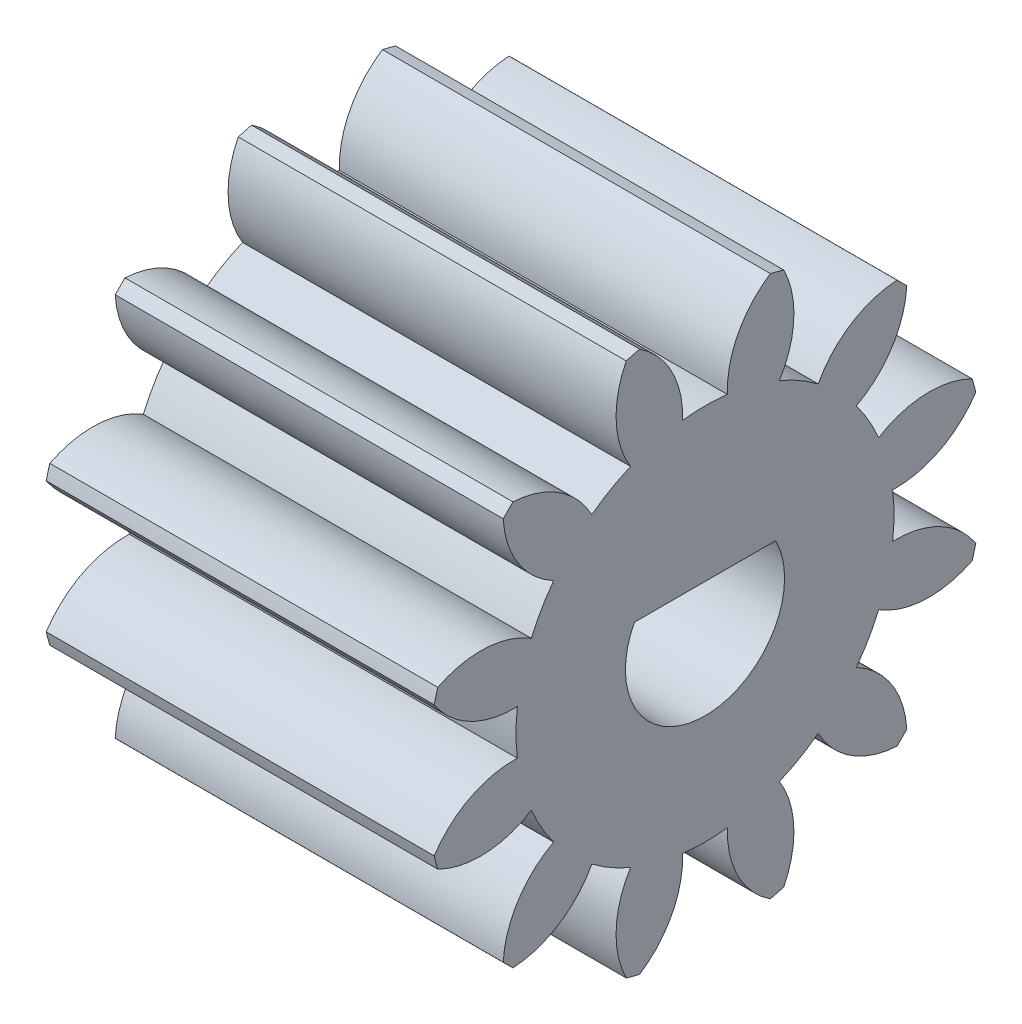
SolidWorks part; units mm, degrees
ref_plane "Plane1" through (0, 0, 0) normal (0, 0, 1) x (1, 0, 0)
ref_plane "Plane2" through (0, 0, 0) normal (0, 1, 0) x (1, 0, 0)
ref_plane "Plane3" through (0, 0, 0) normal (1, 0, 0) x (0, 0, -1)
sketch "HoldingSke" plane through (0, 0, 0) normal (0, 1, 0) x (1, 0, 0)
  line L0 (0, 0) -> (631.0617, -134.1363)
  line L1 (-15, 0) -> (100, 0) construction
  line L2 (0, 0) -> (-2.1039, 2.3779)
  line L3 (0, 0) -> (-11.863, 4.5341)
  line L4 (0, 0) -> (8.4473, 1.7955)
  line L5 (0, 0) -> (-46.8476, -17.4728)
  line L6 (0, 0) -> (-9.9476, -6.7116)
  line L7 (-2.1039, 2.3779) -> (8.6589, 51.2071)
  line L8 (-76.2, 54.61) -> (-76.1, 54.61)
  line L9 (-71.009, 38.7566) -> (-53.1078, 45.2721)
  line L10 (-76.2, 71.12) -> (104.1128, 71.12)
  line L11 (0, 0) -> (-12, 0)
  line L12 (-76.2, 101.6) -> (-76.162, 101.6)
  line L13 (24.9733, 27.94) -> (52.9518, 28.4284)
  line L14 (24.9733, 27.94) -> (24.9743, 27.94)
  line L15 (24.9733, 27.94) -> (100.4006, 29.5858)
  line L16 (-63.627, -1) -> (-12.827, -1)
  circle A0 centre (0, 0) radius 0.4
  circle A1 centre (0, 0) radius 4.749
  circle A2 centre (0, 0) radius 37.5
  circle A3 centre (0, 0) radius 0.4
  dimension "MHD" = 9.498
  dimension "Hub_dia" = 75
  dimension "Bore" = 0.8
  dimension "MBD" = 0.8
  dimension "Num_teeth" = 12
  dimension "Pitch" = 645.16
  dimension "Overall_len" = 50
  dimension "Show_teeth" = 12
  dimension "Thickness" = 12
  dimension "OAL" = 50.0013
  dimension "T_dim" = 0.1
  dimension "Ap" = 20
  dimension "H" = 19.05
  dimension "Pitch_radius" = 180.3128
  dimension "Width" = 12
  dimension "Backlash" = 0.038
  dimension "Addendum_fac" = 1
  dimension "Dedendum_fac" = 1.25
  dimension "Clearance_fac" = 0.25
  dimension "Dedendum_add" = 0.001
  dimension "Module" = 1
sketch "BasProSke" plane through (0, 0, 0) normal (0, 1, 0) x (1, 0, 0)
  line L0 (-10, 0) -> (60, 0) construction
  line L1 (0, 0) -> (0, 7)
  line L2 (0, 0) -> (9.75, 0)
  line L3 (9.75, 0) -> (9.75, 7)
  line L4 (9.75, 7) -> (0, 7)
  dimension "Thickness" = 9.75
  dimension "Diameter" = 14
revolve "Base-Revolve" add sketch "BasProSke" angle 360 about L0
sketch "TooCutSke" plane through (0, 0, 0) normal (1, 0, 0) x (0, 0, -1)
  line L1 (0, 0) -> (0, 107) construction
  line L2 (0, 0) -> (-0.8496, 5.9395) construction
  line L3 (0, 0) -> (-3.0836, 11.5081) construction
  line L4 (-0.8496, 5.9395) -> (-1.5418, 5.7541) construction
  arc A0 (0.5622, 4.7156) -> (-0.5622, 4.7156) centre (0, 0) ccw
  arc A1 (2.6365, 7.1762) -> (-2.6365, 7.1762) centre (0, 0) ccw
  circle A2 centre (0, 0) radius 6 construction
  circle A3 centre (0, 0) radius 5.6382 construction
  arc A4 (-0.5622, 4.7156) -> (-2.6365, 7.1762) centre (-2.9608, 4.7982) ccw
  arc A5 (2.6365, 7.1762) -> (0.5622, 4.7156) centre (2.9608, 4.7982) ccw
  dimension "Root_dia" = 9.498
  dimension "Overcut_dia" = 15.2903
  dimension "Pitch_dia" = 12
  dimension "Base_dia" = 11.2763
  dimension "Flank_rad" = 2.4
  dimension "Half_ang" = 15
  dimension "Half_CT" = 0.7167
extrude "ToothCut" cut sketch "TooCutSke" along normal through all
fillet "Breaks" [suppressed] radius 0.02 tangent propagation no
fillet "RootFillets" [suppressed] radius 0.251
pattern_circular "TeethCuts" count 12 every 30 about axis through (-10, 0, 0) along (1, 0, 0) of "ToothCut", "RootFillets", "Breaks"
sketch "HubNeaOneSke" plane through (0, 0, 0) normal (-1, 0, 0) x (0, 0, 1)
  circle A0 centre (0, 0) radius 4.749
  dimension "Diameter" = 9.498
extrude "HubNearOne" [suppressed] add sketch "HubNeaOneSke" along normal blind 40.2513
sketch "HubNeaBotSke" plane through (0, 0, 0) normal (-1, 0, 0) x (0, 0, 1)
  circle A0 centre (0, 0) radius 4.749
  dimension "Diameter" = 9.498
extrude "HubNearBoth" [suppressed] add sketch "HubNeaBotSke" along normal blind 20.1256
ref_plane "FarPln" through (9.75, 0, 0) normal (1, 0, 0) x (0, 0, -1)
sketch "HubFarSke" plane through (9.75, 0, 0) normal (1, 0, 0) x (0, 0, -1)
  circle A0 centre (0, 0) radius 4.749
  dimension "Diameter" = 9.498
extrude "HubFar" [suppressed] add sketch "HubFarSke" along normal blind 20.1256
sketch "BorSke" plane through (0, 0, 0) normal (1, 0, 0) x (0, 0, -1)
  circle A0 centre (0, 0) radius 0.4
  dimension "Diameter" = 0.8
extrude "Bore" cut sketch "BorSke" along normal mid plane 100.0026
sketch "KeySke" plane through (0, 0, 0) normal (1, 0, 0) x (0, 0, -1)
  line L0 (-0.05, 0) -> (-0.05, 0.5)
  line L1 (-0.05, 0.5) -> (0.05, 0.5)
  line L2 (0.05, 0.5) -> (0.05, 0)
  line L3 (0, 0) -> (0, 34) construction
  line L4 (-0.05, 0) -> (0.05, 0)
  dimension "Offset" = 0.5
  dimension "Width" = 0.1
extrude "Keyway" [suppressed] cut sketch "KeySke" along normal mid plane 100.0026
pattern_circular "Keyway2" [suppressed] count 2 every 90 about axis through (-10, 0, 0) along (1, 0, 0) reverse direction yes
sketch "Sketch1" plane through (0, 0, 0) normal (-1, 0, 0) x (0, 0, 1)
  circle A0 centre (0, 0) radius 7
scale "Scale1" scale about centroid uniform scaling yes scale factor 2
sketch "Sketch4" plane through (14.625, 0, 0) normal (1, 0, 0) x (0, 0, -1)
  line L2 (0, 1.85) -> (-3.5465, 1.85)
  line L3 (0, 1.85) -> (3.5465, 1.85)
  arc A0 (-3.5465, 1.85) -> (3.5465, 1.85) centre (0, 0) ccw
extrude "Cut-Extrude1" cut sketch "Sketch4" against normal blind 15
sketch "Sketch5" plane through (-4.875, 0, 0) normal (-1, 0, 0) x (0, 0, 1)
  circle A0 centre (0, 0) radius 4
extrude "Cut-Extrude2" cut sketch "Sketch5" against normal blind 5
sketch "Sketch6" plane through (14.625, 0, 0) normal (1, 0, 0) x (0, 0, -1)
  circle A0 centre (0, 0) radius 11.811 construction
  dimension "D1" = 23.622
equation "' \"Module@HoldingSke\" = 6.35"
equation "' \"Num_teeth@HoldingSke\" = 12"
equation "' \"Ap@HoldingSke\" =  20"
equation "' \"Ap@HoldingSke\" = 20"
equation "' \"Width@HoldingSke\" = 0.5 * 25.4"
equation "' \"Hub_dia@HoldingSke\"= 1 * 25.4"
equation "' \"Hub_dia@HoldingSke\" = 1 * 25.4"
equation "' \"Overall_len@HoldingSke\" = 1.0 * 25.4"
equation "' \"Bore@HoldingSke\" = 0.75 * 25.4"
equation "' \"T_dim@HoldingSke\" = 0.1 * 25.4"
equation "' \"Width@KeySke\" = 0.25 * 25.4"
equation "' \"Show_teeth@HoldingSke\" = 13"
equation "' \"Backlash@HoldingSke\" = 0.009 * 25.4"
equation "' \"Addendum_fac@HoldingSke\" = 1.0"
equation "' \"Dedendum_fac@HoldingSke\" = 1.25"
equation "' \"Dedendum_add@HoldingSke\" = 0.00005 * 25.4"
equation "' \"Clearance_fac@HoldingSke\" = 0.25"
equation "\"Pitch@HoldingSke\" = 1 / \"Module@HoldingSke\""
equation "\"Overcut_dia@TooCutSke\" = (\"Num_teeth@HoldingSke\" + 2 * \"Addendum_fac@HoldingSke\") / \"Pitch@HoldingSke\" + 0.002 * 25.4"
equation "\"Pitch_dia@TooCutSke\" = \"Num_teeth@HoldingSke\" / \"Pitch@HoldingSke\""
equation "\"Base_dia@TooCutSke\" = \"Num_teeth@HoldingSke\" / \"Pitch@HoldingSke\" * cos((\"Ap@HoldingSke\"  * 3.14159265 / 180))"
equation "\"Root_dia@TooCutSke\" = (\"Num_teeth@HoldingSke\" + 2) / \"Pitch@HoldingSke\" - 2 * (\"Addendum_fac@HoldingSke\" + \"Dedendum_fac@HoldingSke\") / \"Pitch@HoldingSke\" - \"Dedendum_add@HoldingSke\" * 2"
equation "\"Half_ang@TooCutSke\" = 180 / \"Num_teeth@HoldingSke\""
equation "\"Half_CT@TooCutSke\" = \"Num_teeth@HoldingSke\" / \"Pitch@HoldingSke\" * sin((3.14159265 / 2 / \"Num_teeth@HoldingSke\")) / 2 - 7 * \"Backlash@HoldingSke\" / 4"
equation "\"Flank_rad@TooCutSke\" = \"Num_teeth@HoldingSke\" / \"Pitch@HoldingSke\" / 5"
equation "\"Radius@RootFillets\" = \"Clearance_fac@HoldingSke\" / \"Pitch@HoldingSke\" + \"Dedendum_add@HoldingSke\""
equation "\"Break_rad@Breaks\" = 0.02 / \"Pitch@HoldingSke\""
equation "\"Thickness@HoldingSke\" = \"Width@HoldingSke\""
equation "\"OAL@HoldingSke\" = \"Thickness@HoldingSke\""
equation "\"MHD@HoldingSke\" = (\"Num_teeth@HoldingSke\" + 2) / \"Pitch@HoldingSke\" - 2 * (\"Addendum_fac@HoldingSke\" + \"Dedendum_fac@HoldingSke\")  / \"Pitch@HoldingSke\" - \"Dedendum_add@HoldingSke\" * 2"
equation "\"MBD@HoldingSke\" = (\"Num_teeth@HoldingSke\" + 2) / \"Pitch@HoldingSke\" - 2 * (\"Addendum_fac@HoldingSke\" + \"Dedendum_fac@HoldingSke\")  / \"Pitch@HoldingSke\" - \"Dedendum_add@HoldingSke\" * 2 - 0.002 * 25.4"
equation "\"MHD@HoldingSke\" = ((sgn( \"MHD@HoldingSke\" - \"Hub_dia@HoldingSke\" )-1)*( \"MHD@HoldingSke\" - \"Hub_dia@HoldingSke\" ))/-2+ \"Hub_dia@HoldingSke\""
equation "\"MBD@HoldingSke\" = ((sgn( \"MBD@HoldingSke\" - \"Bore@HoldingSke\" )-1)*( \"MBD@HoldingSke\" - \"Bore@HoldingSke\" ))/-2+ \"Bore@HoldingSke\""
equation "\"OAL@HoldingSke\" = ((sgn( \"OAL@HoldingSke\" - \"Overall_len@HoldingSke\" )+1)*( \"OAL@HoldingSke\" - \"Overall_len@HoldingSke\" ))/2 + \"Overall_len@HoldingSke\" + 0.000002 * 25.4"
equation "\"Num_teeth@TeethCuts\" = int( \"Show_teeth@HoldingSke\" ) + 1"
equation "\"Num_teeth@TeethCuts\" = ((sgn( \"Num_teeth@TeethCuts\" - \"Num_teeth@HoldingSke\" )-1)*( \"Num_teeth@TeethCuts\" - \"Num_teeth@HoldingSke\" ))/-2+ \"Num_teeth@HoldingSke\""
equation "\"Num_teeth@TeethCuts\" = ((sgn( \"Num_teeth@TeethCuts\" - 2.0)+1)*( \"Num_teeth@TeethCuts\" - 2.0))/2 +2.0"
equation "\"Angle@TeethCuts\" = 360.0 / \"Num_teeth@HoldingSke\""
equation "\"Diameter@BasProSke\" = (\"Num_teeth@HoldingSke\" + 2 * \"Addendum_fac@HoldingSke\") / \"Pitch@HoldingSke\""
equation "' \"Fillet_rad@BasProSke\" =  \"Thickness@HoldingSke\" * 0.05"
equation "' \"Fillet_rad@BasProSke\" = \"Thickness@HoldingSke\" * 0.05"
equation "\"MHD@HoldingSke\" = ((sgn( \"MHD@HoldingSke\" - \"Root_dia@TooCutSke\" )-1)*( \"MHD@HoldingSke\" - \"Root_dia@TooCutSke\" ))/-2+ \"Root_dia@TooCutSke\""
equation "\"Diameter@HubNeaOneSke\" = \"MHD@HoldingSke\""
equation "\"Length@HubNearOne\" = \"OAL@HoldingSke\" - \"Thickness@BasProSke\""
equation "\"Diameter@HubNeaBotSke\" = \"MHD@HoldingSke\""
equation "\"Length@HubNearBoth\" = ( \"OAL@HoldingSke\" - \"Thickness@BasProSke\" ) / 2.0"
equation "\"Thickness@FarPln\" = \"Thickness@BasProSke\""
equation "\"Diameter@HubFarSke\" = \"MHD@HoldingSke\""
equation "\"Length@HubFar\" = ( \"OAL@HoldingSke\" - \"Thickness@BasProSke\" ) / 2.0"
equation "\"Diameter@BorSke\" = \"MBD@HoldingSke\""
equation "\"D1@Bore\" = \"OAL@HoldingSke\" * 2.0"
equation "\"D1@Keyway\" = \"OAL@HoldingSke\" * 2.0"
equation "\"Offset@KeySke\" = \"T_dim@HoldingSke\" + \"MBD@HoldingSke\" / 2.0"
